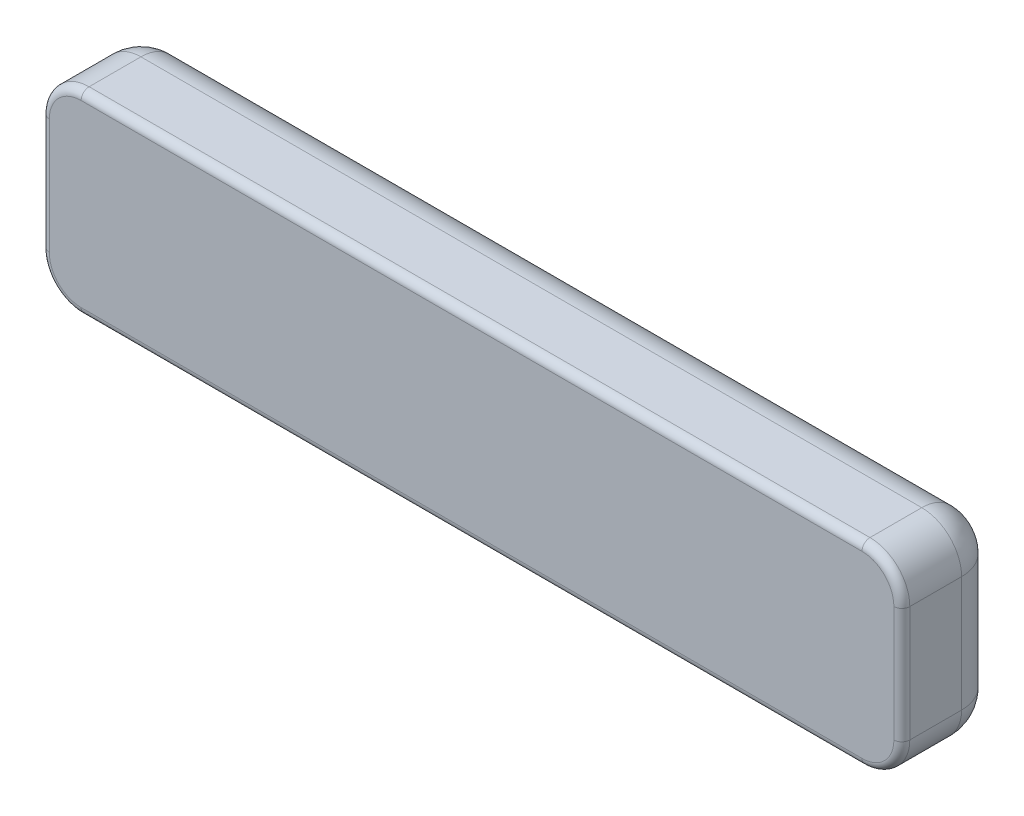
SolidWorks part; units mm, degrees
ref_plane "Front Plane" through (0, 0, 0) normal (0, 0, 1) x (1, 0, 0)
ref_plane "Top Plane" through (0, 0, 0) normal (0, 1, 0) x (1, 0, 0)
ref_plane "Right Plane" through (0, 0, 0) normal (1, 0, 0) x (0, 0, -1)
sketch "Sketch1" plane through (0, 0, 0) normal (0, 0, 1) x (1, 0, 0)
  line L1 (-54, -12.25) -> (54, -12.25)
  line L2 (-54, -12.25) -> (-54, 12.25)
  line L3 (-54, 12.25) -> (54, 12.25)
  line L4 (54, -12.25) -> (54, 12.25)
  line L5 (-54, -12.25) -> (54, 12.25) construction
  line L6 (-54, 12.25) -> (54, -12.25) construction
  point P0 (0, 0)
  dimension "D1" = 108
  dimension "D2" = 24.5
extrude "Boss-Extrude1" add sketch "Sketch1" along normal blind 12.5
fillet "Fillet1" radius 5 4 edges at (-54, 0, 0) (0, -12.25, 0) (54, 0, 0) (0, 12.25, 0)
sketch "Sketch2" plane through (0, 0, 0) normal (0, 0, -1) x (-1, 0, 0)
  line L0 (-25, 0) -> (25, 0) construction
  circle A0 centre (-25, 0) radius 1.8
  circle A1 centre (25, 0) radius 1.8
  point P4 (0, 0)
  dimension "D2" = 3.6
  dimension "D1" = 50
extrude "Cut-Extrude1" cut sketch "Sketch2" against normal blind 5
fillet "Fillet2" radius 5 8 edges at (-52.5355, -10.7855, 1.4645) (-52.5355, 10.7855, 1.4645) (52.5355, -10.7855, 1.4645) (52.5355, 10.7855, 1.4645) (-54, -12.25, 8.75) (-54, 12.25, 8.75) (54, -12.25, 8.75) (54, 12.25, 8.75)
fillet "Fillet3" radius 1 8 edges at (-52.5355, -10.7855, 12.5) (-54, 0, 12.5) (-52.5355, 10.7855, 12.5) (0, -12.25, 12.5) (0, 12.25, 12.5) (52.5355, 10.7855, 12.5) (54, 0, 12.5) (52.5355, -10.7855, 12.5)
